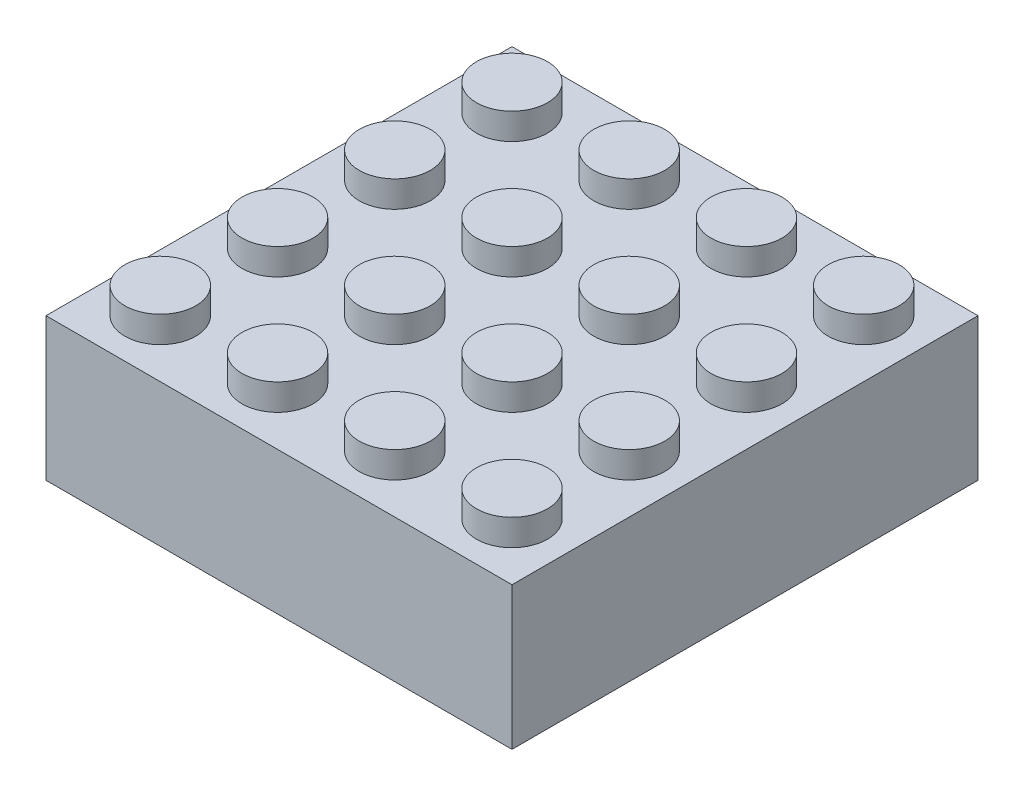
SolidWorks part; units mm, degrees
ref_plane "Front Plane" through (0, 0, 0) normal (0, 0, 1) x (1, 0, 0)
ref_plane "Top Plane" through (0, 0, 0) normal (0, 1, 0) x (1, 0, 0)
ref_plane "Right Plane" through (0, 0, 0) normal (1, 0, 0) x (0, 0, -1)
sketch "Sketch1" plane through (0, 0, 0) normal (0, 1, 0) x (1, 0, 0)
  line L1 (0, 0) -> (31.8, 0)
  line L2 (0, 0) -> (0, 31.8)
  line L3 (0, 31.8) -> (31.8, 31.8)
  line L4 (31.8, 0) -> (31.8, 31.8)
  dimension "D1" = 31.8
  dimension "D2" = 31.8
sketch "Sketch2" plane through (0, 0, 0) normal (0, 1, 0) x (1, 0, 0)
  line L0 (0, 0) -> (0, 31.8) construction
  line L1 (0, 31.8) -> (31.8, 31.8) construction
  circle A0 centre (3.9, 27.9) radius 2.425
  circle A1 centre (11.9, 27.9) radius 2.425
  circle A2 centre (19.9, 27.9) radius 2.425
  circle A3 centre (27.9, 27.9) radius 2.425
  circle A4 centre (11.9, 19.9) radius 2.425
  circle A5 centre (19.9, 19.9) radius 2.425
  circle A6 centre (27.9, 19.9) radius 2.425
  circle A7 centre (11.9, 11.9) radius 2.425
  circle A8 centre (19.9, 11.9) radius 2.425
  circle A9 centre (27.9, 11.9) radius 2.425
  circle A10 centre (11.9, 3.9) radius 2.425
  circle A11 centre (19.9, 3.9) radius 2.425
  circle A12 centre (27.9, 3.9) radius 2.425
  circle A13 centre (3.9, 19.9) radius 2.425
  circle A14 centre (3.9, 11.9) radius 2.425
  circle A15 centre (3.9, 3.9) radius 2.425
  dimension "D3" = 4.85
  dimension "D1" = 3.9
  dimension "D2" = 3.9
  dimension "D4" = 4
  dimension "D5" = 4
extrude "Boss-Extrude1" add sketch "Sketch2" along normal blind 1.8
extrude "Boss-Extrude2" add sketch "Sketch1" against normal blind 9.73
sketch "Sketch4" plane through (0, -9.73, 0) normal (0, -1, 0) x (1, 0, 0)
  line L1 (26.0857, -15.8744) -> (21.0164, -7.0925)
  line L2 (21.0164, -7.0925) -> (10.8054, -7.0798)
  line L3 (10.8054, -7.0798) -> (5.7143, -15.9291)
  line L4 (5.7143, -15.9291) -> (10.8306, -24.7346)
  line L5 (10.8306, -24.7346) -> (21.0154, -24.7081)
  line L6 (21.0154, -24.7081) -> (26.0857, -15.8744)
  circle A0 centre (15.9, -15.9) radius 10.1858
  point P40 (15.9, -15.9)
  dimension "D1" = 20.3715
extrude "Cut-Extrude1" cut sketch "Sketch4" against normal blind 6.63 contours L6 L1 L2 L3 L4 L5 region at (15.9038, -9.73, -15.9011)
sketch "Sketch9" plane through (0, -9.73, 0) normal (0, -1, 0) x (1, 0, 0)
  line L0 (21.0164, -7.0925) -> (10.8054, -7.0798) construction
  line L2 (11.8054, -7.0811) -> (20.0165, -7.0811)
  line L3 (11.8054, -7.0811) -> (11.8054, -5.3311)
  line L4 (11.8054, -5.3311) -> (20.0165, -5.3311)
  line L5 (20.0165, -7.0811) -> (20.0165, -5.3311)
  dimension "D1" = 1
  dimension "D2" = 1
  dimension "D3" = 1.75
extrude "Boss-Extrude4" add sketch "Sketch9" along normal blind 1.5
sketch "Sketch10" plane through (20.0165, 0, 0) normal (1, 0, 0) x (0, 0, -1)
  line L2 (7.0811, -11.23) -> (7.9811, -9.83)
  line L4 (7.9811, -9.83) -> (7.0811, -9.73)
  line L5 (7.0811, -11.23) -> (7.0811, -9.73)
  dimension "D3" = 1.4
  dimension "D4" = 0.9
extrude "Boss-Extrude5" add sketch "Sketch10" against normal up to surface (8.211 mm away) up to face at (11.8054, -10.48, -6.2061)
sketch "Sketch11" plane through (20.0165, 0, 0) normal (1, 0, 0) x (0, 0, -1)
  line L0 (6.3311, -11.23) -> (5.3311, -9.73)
  line L1 (7.0811, -11.23) -> (5.3311, -11.23) construction
  line L2 (5.3311, -9.73) -> (5.3311, -11.23)
  line L3 (5.3311, -11.23) -> (6.3311, -11.23)
  dimension "D1" = 1
extrude "Cut-Extrude4" cut sketch "Sketch11" against normal up to next (8.211 mm away)
ref_axis "Axis2" through (15.9, 33.0797, -15.9) along (0, -1, 0)
pattern_circular "CirPattern3" count 6 over 360 about axis through (15.9, 33.0797, -15.9) along (0, -1, 0) of "Boss-Extrude4", "Boss-Extrude5", "Cut-Extrude4"
sketch "Sketch12" plane through (12.6929, 0, 7.3269) normal (-0.8661, 0, -0.4999) x (-0.4999, 0, 0.8661)
  line L0 (-21.7193, -3.1) -> (-21.7193, -7.8799)
  line L1 (-26.7894, -3.1) -> (-16.6493, -3.1) construction
sketch "Sketch13" plane through (0, -3.1, 0) normal (0, -1, 0) x (1, 0, 0)
  line L0 (23.5511, -11.4835) -> (8.2724, -20.3319)
  line L1 (26.0857, -15.8744) -> (21.0164, -7.0925) construction
  line L2 (5.7143, -15.9291) -> (10.8306, -24.7346) construction
ref_plane "Plane1" through (10.8952, 0, -18.8129) normal (-0.5012, 0, 0.8654) x (0.8654, 0, 0.5012)
sketch "Sketch14" plane through (10.8952, 0, -18.8129) normal (-0.5012, 0, 0.8654) x (0.8654, 0, 0.5012)
  line L0 (14.625, -3.1) -> (14.625, -8.6397)
  line L1 (14.625, -8.6397) -> (14.025, -3.1)
  line L2 (14.025, -3.1) -> (14.625, -3.1)
  dimension "D1" = 0.6
extrude "Boss-Extrude6" add sketch "Sketch14" along normal blind 0.3 and the other way blind 0.3
pattern_circular "CirPattern4" count 6 over 360 about axis through (15.9, 33.0797, -15.9) along (0, -1, 0) of "Boss-Extrude6"
sketch "Sketch18" plane through (11.8054, 0, 0) normal (-1, 0, 0) x (0, 0, 1)
  line L0 (-7.0811, -11.23) -> (-7.0811, -9.73)
  line L6 (-7.0811, -11.23) -> (-6.3311, -11.23)
  line L7 (-6.3311, -11.23) -> (-5.3311, -9.73)
  line L8 (-5.3311, -9.73) -> (-7.0811, -9.73)
  line L9 (-7.0811, -9.73) -> (-7.9811, -9.83)
  line L10 (-7.9811, -9.83) -> (-7.0811, -11.23)
  line L11 (-7.0811, -11.23) -> (-6.3311, -11.23)
  line L12 (-6.3311, -11.23) -> (-5.3311, -9.73)
  line L13 (-5.3311, -9.73) -> (-7.0811, -9.73)
  dimension "D1" = 0
extrude "Boss-Extrude7" add sketch "Sketch18" along normal blind 2
pattern_circular "CirPattern5" count 6 over 360 about axis through (15.9, 33.0797, -15.9) along (0, -1, 0) of "Boss-Extrude7"
ref_plane "Plane2" through (15.9197, 0, -0.0197) normal (1, 0, -0.0012) x (0, -1, 0)
mirror "Mirror1" about plane through (15.9197, 0, -0.0197) normal (1, 0, -0.0012) of "Boss-Extrude7"
mirror "Mirror2" about plane through (15.9197, 0, -0.0197) normal (1, 0, -0.0012) of "CirPattern5"
